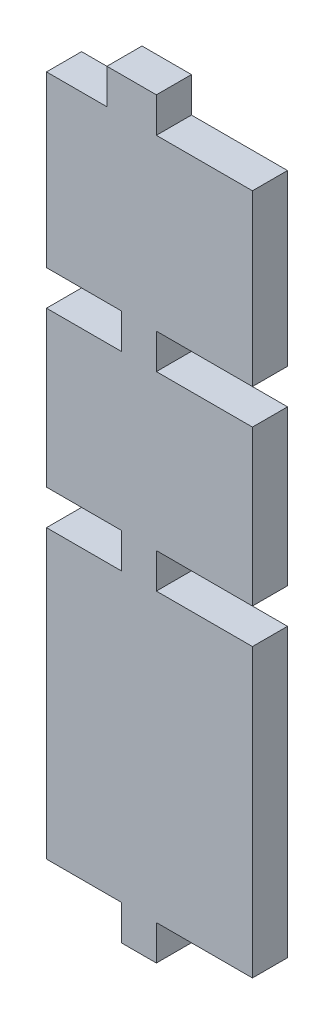
SolidWorks part; units mm, degrees
ref_plane "Front Plane" through (0, 0, 0) normal (0, 0, 1) x (1, 0, 0)
ref_plane "Top Plane" through (0, 0, 0) normal (0, 1, 0) x (1, 0, 0)
ref_plane "Right Plane" through (0, 0, 0) normal (1, 0, 0) x (0, 0, -1)
sketch "Sketch1" plane through (0, 0, 0) normal (0, 0, 1) x (1, 0, 0)
  line L0 (4.2711, -1.524) -> (4.2711, 0)
  line L1 (4.2711, -1.524) -> (1.0213, -1.524)
  line L2 (1.0213, -1.524) -> (1.0213, -13.9935)
  line L3 (4.2711, 0) -> (1.0213, 0)
  line L4 (1.0213, 0) -> (1.0213, 6.7327)
  line L5 (4.2711, 8.2567) -> (4.2711, 6.7327)
  line L6 (4.2711, 6.7327) -> (1.0213, 6.7327)
  line L7 (4.2711, 8.2567) -> (1.0213, 8.2567)
  line L8 (1.0213, 8.2567) -> (1.0213, 15.6227)
  line L9 (5.0331, 0) -> (5.0331, 6.7327) construction
  line L12 (9.9679, -1.524) -> (9.9679, -13.9935)
  line L13 (5.7951, 0) -> (9.9679, 0)
  line L14 (5.7951, -1.524) -> (9.9679, -1.524)
  line L15 (5.7951, -1.524) -> (5.7951, 0)
  line L16 (9.9679, 8.2567) -> (9.9679, 15.6227)
  line L17 (5.7951, 8.2567) -> (9.9679, 8.2567)
  line L18 (5.7951, 6.7327) -> (9.9679, 6.7327)
  line L19 (5.7951, 8.2567) -> (5.7951, 6.7327)
  line L20 (9.9679, 0) -> (9.9679, 6.7327)
  line L21 (1.0213, -13.9935) -> (4.2711, -13.9935)
  line L22 (9.9679, 15.6227) -> (5.7951, 15.6227)
  line L23 (5.0331, 15.6227) -> (5.0331, 17.1467) construction
  line L24 (5.0331, -13.9935) -> (5.0331, -15.5175) construction
  line L25 (4.2711, -13.9935) -> (4.2711, -15.5175)
  line L26 (5.7951, 15.6227) -> (5.7951, 17.1467)
  line L27 (5.7951, -13.9935) -> (5.7951, -15.5175)
  line L28 (3.6464, 15.6227) -> (3.6464, 17.1467)
  line L30 (4.2711, -15.5175) -> (5.7951, -15.5175)
  line L31 (3.6464, 15.6227) -> (1.0213, 15.6227)
  line L32 (5.7951, 17.1467) -> (3.6464, 17.1467)
  line L33 (5.7951, -13.9935) -> (9.9679, -13.9935)
extrude "Boss-Extrude1" add sketch "Sketch1" along normal blind 1.524
